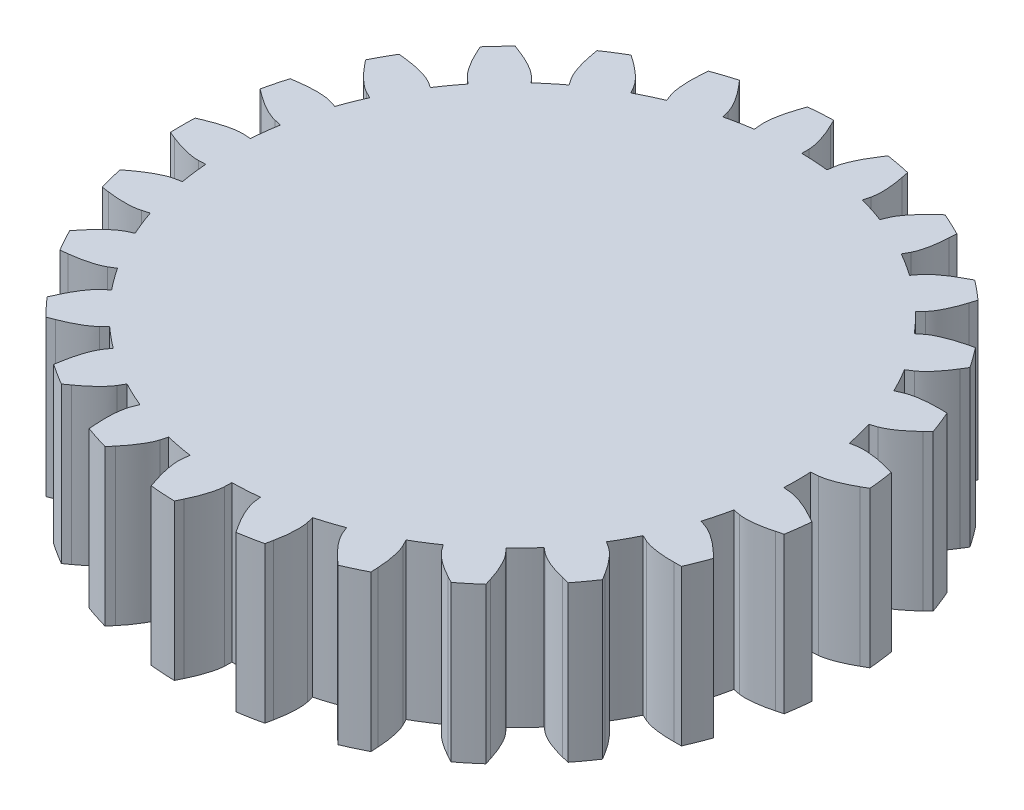
SolidWorks part; units mm, degrees
ref_plane "Front Plane" through (0, 0, 0) normal (0, 0, 1) x (1, 0, 0)
ref_plane "Top Plane" through (0, 0, 0) normal (0, 1, 0) x (1, 0, 0)
ref_plane "Right Plane" through (0, 0, 0) normal (1, 0, 0) x (0, 0, -1)
sketch "Sketch1" plane through (0, 0, 0) normal (0, 1, 0) x (1, 0, 0)
  line L0 (0, 30) -> (-129.8026, 30) construction
  line L1 (-99.777, -6.3159) -> (118.111, 72.9889) construction
  circle A0 centre (0, 0) radius 30
  circle A1 centre (0, 0) radius 28.1908
  point P8 (-99.777, 0)
  point P9 (118.111, 72.9889)
  point P10 (-129.8026, 30)
  point P11 (0, 0)
  dimension "D1" = 60
  dimension "D2" = 20
sketch "Sketch2" plane through (0, 0, 0) normal (0, 1, 0) x (1, 0, 0)
  line L0 (0, 0) -> (-9.6418, 26.4907) construction
  line L1 (-99.777, -6.3159) -> (118.111, 72.9889) construction
  line L2 (-9.6418, 26.4907) -> (0, 30)
  line L3 (-10.3543, 26.2204) -> (0, 0) construction
  line L4 (-10.3543, 26.2204) -> (-0.1021, 30.2689) construction
  line L5 (0, 0) -> (-11.0591, 25.931) construction
  line L6 (0, 0) -> (-11.7559, 25.6226) construction
  line L7 (-12.4441, 25.2955) -> (0, 0) construction
  line L8 (0, 0) -> (-13.1232, 24.95) construction
  line L9 (-8.9223, 26.7416) -> (0.088, 29.7479) construction
  line L10 (-11.0591, 25.931) -> (-0.2192, 30.554) construction
  line L11 (-11.7559, 25.6226) -> (-0.3523, 30.8547) construction
  line L12 (-12.4441, 25.2955) -> (-0.5023, 31.1703) construction
  line L13 (-6.7269, 27.3764) -> (0.2773, 29.0975) construction
  line L14 (-7.4643, 27.1846) -> (0.2256, 29.2961) construction
  line L15 (-5.9846, 27.5482) -> (0.319, 28.9176) construction
  line L16 (-8.1963, 26.973) -> (0.1629, 29.5131) construction
  line L17 (-5.2378, 27.6999) -> (0.3517, 28.7569) construction
  circle A0 centre (0, 0) radius 28.1908 construction
  arc A1 (-9.6418, 26.4907) -> (-10.3543, 26.2204) centre (0, 0) ccw
  arc A2 (-10.3543, 26.2204) -> (-11.0591, 25.931) centre (0, 0) ccw
  arc A3 (-11.0591, 25.931) -> (-11.7559, 25.6226) centre (0, 0) ccw
  arc A4 (-11.7559, 25.6226) -> (-12.4441, 25.2955) centre (0, 0) ccw
  arc A5 (-12.4441, 25.2955) -> (-13.1232, 24.95) centre (0, 0) ccw
  arc A6 (-9.6418, 26.4907) -> (-8.9223, 26.7416) centre (0, 0) cw
  arc A7 (-8.9223, 26.7416) -> (-8.1963, 26.973) centre (0, 0) cw
  arc A8 (-8.1963, 26.973) -> (-7.4643, 27.1846) centre (0, 0) cw
  arc A9 (-7.4643, 27.1846) -> (-6.7269, 27.3764) centre (0, 0) cw
  arc A10 (-6.7269, 27.3764) -> (-5.9846, 27.5482) centre (0, 0) cw
  arc A11 (-5.9846, 27.5482) -> (-5.2378, 27.6999) centre (0, 0) cw
  point P28 (0, 0)
  dimension "D1" = 10.2606
  dimension "D3" = 11.0226
  dimension "D8" = 11.7846
  dimension "D9" = 12.5466
  dimension "D10" = 13.3086
  dimension "D15" = 9.4986
  dimension "D16" = 8.7366
  dimension "D17" = 7.9746
  dimension "D18" = 7.2126
  dimension "D21" = 6.4506
  dimension "D22" = 5.6886
  dimension "D2" = 0.762
  dimension "D4" = 0.762
  dimension "D5" = 0.762
  dimension "D6" = 0.762
  dimension "D7" = 0.762
  dimension "D11" = 0.762
  dimension "D12" = 0.762
  dimension "D13" = 0.762
  dimension "D14" = 0.762
  dimension "D19" = 0.762
  dimension "D20" = 0.762
sketch "Sketch4" plane through (0, 0, 0) normal (0, 1, 0) x (1, 0, 0)
  line L0 (0, 0) -> (0, 39.7853) construction
  line L1 (0, 0) -> (-2.5084, 39.8703) construction
  circle A0 centre (0, 0) radius 28.1908 construction
  circle A1 centre (0, 0) radius 31.81
  circle A2 centre (0, 0) radius 30 construction
  spline S0 degree 3 poles (-0.5023, 31.1703) (-0.4025, 30.9674) (-0.2649, 30.6686) (-0.1033, 30.2758) (-0.0012, 30.0069) (0.0869, 29.7547) (0.1619, 29.52) (0.2247, 29.303) (0.2766, 29.1044) (0.3615, 28.7384) (0.4102, 28.4344) (0.4191, 28.1877) knots 0 0 0 0 0.215965 0.31411 0.405697 0.490726 0.569196 0.641109 0.706463 0.765259 1 1 1 1
  spline S1 degree 3 poles (-3.4083, 30.9875) (-3.4819, 30.7737) (-3.581, 30.46) (-3.692, 30.05) (-3.7597, 29.7704) (-3.8155, 29.5092) (-3.8604, 29.2669) (-3.8956, 29.0438) (-3.9221, 28.8402) (-3.9605, 28.4664) (-3.9707, 28.1588) (-3.9486, 27.9129) knots 0 0 0 0 0.215965 0.31411 0.405697 0.490726 0.569196 0.641109 0.706463 0.765259 1 1 1 1
  spline S2 degree 2 poles (-3.4083, 30.9875) (-3.2603, 31.434) (-3.1869, 31.65) knots 0 0 0 1 1 1
  spline S3 degree 2 poles (-0.5023, 31.1703) (-0.7051, 31.5947) (-0.805, 31.7998) knots 0 0 0 1 1 1
  dimension "D2" = 1.81
  dimension "D1" = 3.6
sketch "Sketch5" plane through (0, 0, 0) normal (0, 1, 0) x (1, 0, 0)
  circle A1 centre (0, 0) radius 27.5
  dimension "D1" = 55
extrude "Boss-Extrude1" add sketch "Sketch5" along normal blind 15
sketch "Sketch7" plane through (0, 0, 0) normal (0, 1, 0) x (1, 0, 0)
  line L0 (0.4191, 28.1877) -> (0.4191, 27.4968)
  circle A2 centre (0, 0) radius 27.5
  arc A3 (0.4191, 27.4968) -> (-3.8796, 27.225) centre (0, 0) ccw
  circle A5 centre (0, 0) radius 31.81
  arc A6 (-0.805, 31.7998) -> (-3.1869, 31.65) centre (0, 0) ccw
  spline S2 degree 2 poles (1274.8199, -2684.1688) (-1275.8104, 2748.1183) (1273.1943, -2684.1016) knots -109.339646 -109.339646 -109.339646 113.20807 113.20807 113.20807 only from (-0.5023, 31.1703) to (-0.805, 31.7998)
  spline S3 degree 2 poles (-0.5023, 31.1703) (-0.7051, 31.5947) (-0.805, 31.7998) knots 0 0 0 1 1 1
  spline S5 degree 3 poles (2998.75, -30.18) (-181.7072, 31.7269) (-13.9419, 63.9356) (-0.1033, 30.2758) (-0.0012, 30.0069) (0.0869, 29.7547) (0.1619, 29.52) (0.2247, 29.303) (0.2766, 29.1044) (3.4004, 15.6431) (-35.1593, -6.9752) (-2993.4136, -158.0668) knots -34.354648 -34.354648 -34.354648 -34.354648 0.215965 0.31411 0.405697 0.490726 0.569196 0.641109 0.706463 0.765259 13.840232 13.840232 13.840232 13.840232 only from (-0.5023, 31.1703) to (0.4191, 28.1877)
  spline S6 degree 3 poles (-0.5023, 31.1703) (-0.4025, 30.9674) (-0.2649, 30.6686) (-0.1033, 30.2758) (-0.0012, 30.0069) (0.0869, 29.7547) (0.1619, 29.52) (0.2247, 29.303) (0.2766, 29.1044) (0.3615, 28.7384) (0.4102, 28.4344) (0.4191, 28.1877) knots 0 0 0 0 0.215965 0.31411 0.405697 0.490726 0.569196 0.641109 0.706463 0.765259 1 1 1 1
  spline S8 degree 2 poles (-928.352, -2822.7807) (921.3197, 2886.35) (-926.7476, -2822.5102) knots -109.339646 -109.339646 -109.339646 113.20807 113.20807 113.20807 only from (-3.4083, 30.9875) to (-3.1869, 31.65)
  spline S9 degree 2 poles (-3.4083, 30.9875) (-3.2603, 31.434) (-3.1869, 31.65) knots 0 0 0 1 1 1
  spline S10 degree 1 poles (-3.9486, 27.9129) (-3.8796, 27.225) knots 0 0 1 1
  spline S11 degree 3 poles (-2971.3214, -405.785) (176.2979, 54.2507) (5.8187, 65.1788) (-3.692, 30.05) (-3.7597, 29.7704) (-3.8155, 29.5092) (-3.8604, 29.2669) (-3.8956, 29.0438) (-3.9221, 28.8402) (-5.3342, 15.0936) (35.7563, -2.5136) (2989.6206, 218.3538) knots -34.354648 -34.354648 -34.354648 -34.354648 0.215965 0.31411 0.405697 0.490726 0.569196 0.641109 0.706463 0.765259 13.840232 13.840232 13.840232 13.840232 only from (-3.4083, 30.9875) to (-3.9486, 27.9129)
  spline S12 degree 3 poles (-3.4083, 30.9875) (-3.4819, 30.7737) (-3.581, 30.46) (-3.692, 30.05) (-3.7597, 29.7704) (-3.8155, 29.5092) (-3.8604, 29.2669) (-3.8956, 29.0438) (-3.9221, 28.8402) (-3.9605, 28.4664) (-3.9707, 28.1588) (-3.9486, 27.9129) knots 0 0 0 0 0.215965 0.31411 0.405697 0.490726 0.569196 0.641109 0.706463 0.765259 1 1 1 1
  dimension "D1" = 0
  dimension "D2" = 0
  dimension "D3" = 0
  dimension "D4" = 0
  dimension "D5" = 0
  dimension "D6" = 0
extrude "Boss-Extrude2" add sketch "Sketch7" along normal blind 15
sketch "Sketch8" plane through (0, 0, 0) normal (1, 0, 0) x (0, 0, -1)
  line L0 (0, 0) -> (-0.0016, 15) construction
  line L1 (27.4968, 15) -> (-27.5, 15) construction
pattern_circular "CirPattern2" count 25 over 360 about axis through (0, 15, 0) along (0, 1, 0) of "Boss-Extrude2"
equation "\"D3@Sketch2\"=\"D1@Sketch2\"+\"D2@Sketch2\""
equation "\"D4@Sketch2\"=\"D2@Sketch2\""
equation "\"D5@Sketch2\"=\"D2@Sketch2\""
equation "\"D6@Sketch2\"=\"D2@Sketch2\""
equation "\"D7@Sketch2\"=\"D2@Sketch2\""
equation "\"D8@Sketch2\"=\"D3@Sketch2\"+\"D2@Sketch2\""
equation "\"D9@Sketch2\"=\"D8@Sketch2\"+\"D2@Sketch2\""
equation "\"D12@Sketch2\"=\"D11@Sketch2\""
equation "\"D13@Sketch2\"=\"D12@Sketch2\""
equation "\"D14@Sketch2\"=\"D12@Sketch2\""
equation "\"D15@Sketch2\"=\"D1@Sketch2\"-\"D11@Sketch2\""
equation "\"D16@Sketch2\"=\"D15@Sketch2\"-\"D11@Sketch2\""
equation "\"D17@Sketch2\"=\"D16@Sketch2\"-\"D11@Sketch2\""
equation "\"D18@Sketch2\"=\"D17@Sketch2\"-\"D11@Sketch2\""
equation "\"D10@Sketch2\"=\"D1@Sketch2\" + 4*\"D11@Sketch2\""
equation "\"D21@Sketch2\"=\"D18@Sketch2\"-\"D11@Sketch2\""
equation "\"D22@Sketch2\"=\"D21@Sketch2\"-\"D11@Sketch2\""
